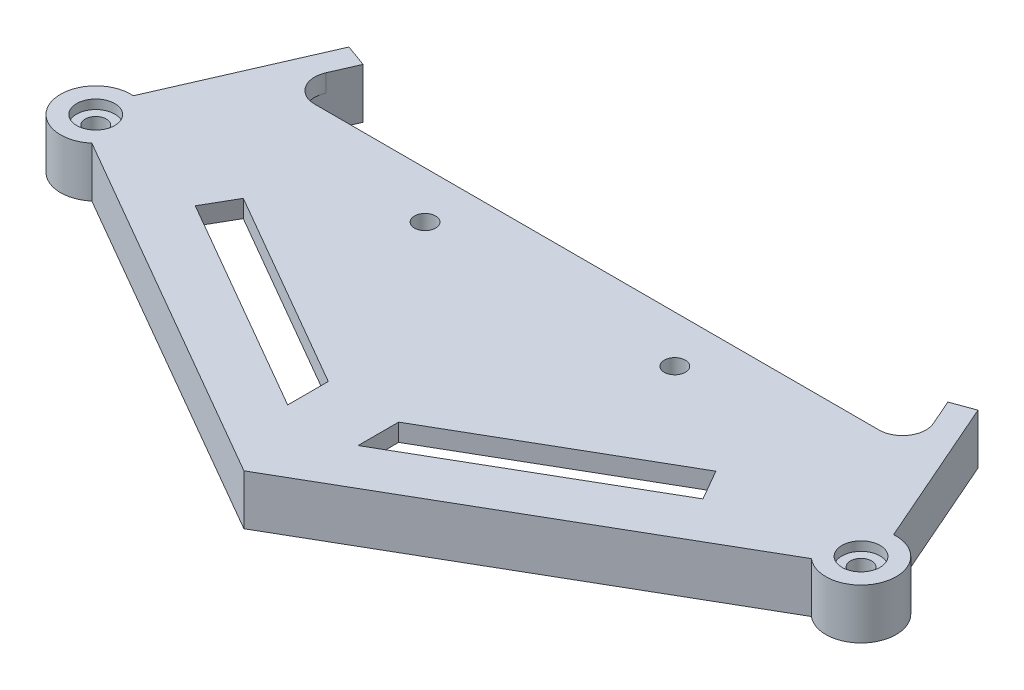
SolidWorks part; units mm, degrees
ref_plane "Front Plane" through (0, 0, 0) normal (0, 0, 1) x (1, 0, 0)
ref_plane "Top Plane" through (0, 0, 0) normal (0, 1, 0) x (1, 0, 0)
ref_plane "Right Plane" through (0, 0, 0) normal (1, 0, 0) x (0, 0, -1)
sketch "Sketch1" plane through (0, 0, 0) normal (0, 1, 0) x (1, 0, 0)
  line L0 (-2, 1.1547) -> (-61.3696, 35.4318)
  line L1 (-65.2686, 39.9923) -> (-42.6286, 26.921) construction
  line L2 (-2, 1.1547) -> (0, 0)
  line L3 (0, 4.6188) -> (-59.3696, 38.8959)
  line L4 (2, 1.1547) -> (0, 0)
  line L5 (2, 1.1547) -> (61.3696, 35.4318)
  line L6 (0, 4.6188) -> (59.3696, 38.8959)
  line L7 (-65.2686, 45.9923) -> (65.2686, 45.9923) construction
  line L8 (-65.2686, 39.9923) -> (-58.4065, 67.9795) construction
  line L9 (-58.4065, 67.9795) -> (-56.6964, 72.6779) construction
  line L10 (-56.6964, 72.6779) -> (-46.8296, 69.0867) construction
  line L11 (-46.8296, 69.0867) -> (-65.2686, 39.9923) construction
  line L12 (-51.763, 70.8823) -> (-65.2686, 39.9923) construction
  line L13 (-51.763, 70.8823) -> (-49.8799, 70.1969)
  line L14 (-49.8799, 70.1969) -> (-61.17, 44.3742)
  line L15 (-51.763, 70.8823) -> (-53.6461, 71.5677)
  line L16 (-53.6461, 71.5677) -> (-64.835, 45.9766)
  line L17 (0, 4.6188) -> (0, 66.7338) construction
  line L18 (49.8799, 70.1969) -> (61.17, 44.3742)
  line L19 (51.763, 70.8823) -> (49.8799, 70.1969)
  line L20 (51.763, 70.8823) -> (53.6461, 71.5677)
  line L21 (53.6461, 71.5677) -> (64.835, 45.9766)
  line L22 (-54.252, 60.1969) -> (54.252, 60.1969)
  line L23 (-49.8799, 70.1969) -> (49.8799, 70.1969) construction
  circle A0 centre (-65.2686, 39.9923) radius 6
  circle A1 centre (65.2686, 39.9923) radius 6
  circle A2 centre (-65.2686, 39.9923) radius 1.8
  circle A3 centre (65.2686, 39.9923) radius 1.8
  dimension "D1" = 12
  dimension "D7" = 3.6
  dimension "D8" = 3.6
  dimension "D2" = 2
  dimension "D3" = 68.5541
  dimension "D4" = 2.3094
  dimension "D5" = 68.5541
  dimension "D6" = 120
  dimension "D9" = 5
  dimension "D10" = 27.9872
  dimension "D11" = 34.4454
  dimension "D12" = 10.5
  dimension "D13" = 87.635
  dimension "D14" = 2
  dimension "D15" = 2
  dimension "D16" = 10
extrude "Boss-Extrude1" add sketch "Sketch1" along normal blind 4 contours A2 A0 | A1 L6 L3 A0 L0 L2 L4 L5 | A1 A3 | A1 L7 A0 L3 L6 | A0 L14 L13 L15 L16 | A1 L21 L20 L19 L18 region at (-31.041, 0, -19.4083) region at (-70.8075, 0, -38.172) region at (-57.3339, 0, -58.133) region at (0, 0, -39.497) region at (60.2194, 0, -37.0771) region at (57.3339, 0, -58.133)
fillet "Fillet1" radius 4 2 edges at (54.252, 2, -60.1969) (-54.252, 2, -60.1969)
sketch "Sketch2" plane through (0, 4, 0) normal (0, 1, 0) x (1, 0, 0)
  line L0 (-65.2686, 45.9923) -> (65.2686, 45.9923)
  line L4 (61.3696, 35.4318) -> (0, 0) construction
  line L5 (-61.3696, 35.4318) -> (0, 0)
  line L6 (0, 0) -> (61.3696, 35.4318)
  arc A0 (-64.835, 45.9766) -> (-61.3696, 35.4318) centre (-65.2686, 39.9923) ccw construction
  arc A1 (61.3696, 35.4318) -> (64.835, 45.9766) centre (65.2686, 39.9923) ccw construction
  arc A4 (65.2686, 45.9923) -> (61.3696, 35.4318) centre (65.2686, 39.9923) cw
  arc A5 (-65.2686, 45.9923) -> (-61.3696, 35.4318) centre (-65.2686, 39.9923) ccw
  circle A6 centre (-65.2686, 39.9923) radius 1.8
  circle A7 centre (65.2686, 39.9923) radius 1.8
extrude "Boss-Extrude2" [suppressed] add sketch "Sketch2" along normal blind 3 separate body
sketch "Sketch3" plane through (0, 0, 0) normal (0, -1, 0) x (1, 0, 0)
  circle A0 centre (-65.2686, -39.9923) radius 6
  circle A1 centre (65.2686, -39.9923) radius 6
extrude "Cut-Extrude1" [suppressed] cut sketch "Sketch3" against normal up to next
sketch "Sketch4" plane through (0, 4, 0) normal (0, 1, 0) x (1, 0, 0)
  line L5 (43.3013, 35) -> (40.3013, 40.1962)
  line L6 (40.3013, 40.1962) -> (0, 16.9282)
  line L7 (0, 10) -> (43.3013, 35)
  line L8 (-2, 1.1547) -> (-61.3696, 35.4318) construction
  line L15 (61.3696, 35.4318) -> (57.9342, 41.3821) construction
  line L16 (0, 0) -> (0, 10) construction
  line L17 (-43.3013, 35) -> (-40.3013, 40.1962)
  line L18 (0, 10) -> (-43.3013, 35)
  line L19 (-40.3013, 40.1962) -> (0, 16.9282)
  line L22 (0, 16.9282) -> (0, 45.9923) construction
  line L23 (-6, 20.3923) -> (-6, 13.4641)
  line L24 (6, 20.3923) -> (6, 13.4641)
  line L25 (2, 1.1547) -> (61.3696, 35.4318) construction
  dimension "D1" = 50
  dimension "D2" = 50
  dimension "D3" = 6
  dimension "D4" = 6
  dimension "D5" = 10
extrude "Cut-Extrude2" cut sketch "Sketch4" against normal up to next contours L7 L5 | L23 L19 L17 L18 region at (23.9111, 4, -27.2208) region at (-23.9111, 4, -27.2208)
sketch "Sketch5" plane through (0, 0, 0) normal (0, -1, 0) x (1, 0, 0)
  line L0 (-59.3696, -38.8959) -> (0, -4.6188)
  line L1 (0, -4.6188) -> (59.3696, -38.8959)
  line L2 (-61.3696, -35.4318) -> (0, 0)
  line L3 (0, 0) -> (61.3696, -35.4318)
  line L4 (61.17, -44.3742) -> (49.8799, -70.1969)
  line L5 (49.8799, -70.1969) -> (53.6461, -71.5677)
  line L6 (53.6461, -71.5677) -> (64.835, -45.9766)
  line L7 (-65.2686, -45.9923) -> (-53.6461, -71.5677)
  line L8 (-53.6461, -71.5677) -> (-49.8799, -70.1969)
  line L9 (-49.8799, -70.1969) -> (-61.17, -44.3742)
  arc A0 (59.3696, -38.8959) -> (61.3696, -35.4318) centre (65.2686, -39.9923) cw
  arc A1 (-61.3696, -35.4318) -> (-59.3696, -38.8959) centre (-65.2686, -39.9923) cw
  circle A2 centre (-65.2686, -39.9923) radius 6 construction
  arc A3 (61.17, -44.3742) -> (65.2686, -45.9923) centre (65.2686, -39.9923) ccw
  arc A4 (-61.17, -44.3742) -> (-65.2686, -45.9923) centre (-65.2686, -39.9923) cw
  line M7 (61.3696, -35.4318) -> (0, 0)
  line M8 (0, 0) -> (-61.3696, -35.4318)
  line M26 (-64.835, -45.9766) -> (-53.6461, -71.5677)
  line M27 (-53.6461, -71.5677) -> (-49.8799, -70.1969)
  line M28 (-49.8799, -70.1969) -> (-51.8026, -65.7993)
  line M32 (51.8026, -65.7993) -> (49.8799, -70.1969)
  line M33 (49.8799, -70.1969) -> (53.6461, -71.5677)
  line M34 (53.6461, -71.5677) -> (64.835, -45.9766)
extrude "Boss-Extrude3" add sketch "Sketch5" along normal blind 5.558 contours L9 A4 M26 M27 M28 | A1 L0 L1 A0 M8 M7 | A3 L4 M32 M33 M34 region at (-58.9574, 0, -36.3485) region at (57.3339, 0, -58.133) region at (-57.3339, 0, -58.133)
sketch "Sketch6" plane through (0, 0, 0) normal (0, -1, 0) x (1, 0, 0)
  line L0 (-21.3, -52.1969) -> (21.3, -52.1969) construction
  line L1 (-65.2686, -45.9923) -> (65.2686, -45.9923) construction
  line L2 (-54.252, -60.1969) -> (54.252, -60.1969) construction
  circle A0 centre (-21.3, -52.1969) radius 1.8
  circle A1 centre (21.3, -52.1969) radius 1.8
  point P4 (0, -52.1969)
  point P7 (0, -45.9923)
  dimension "D3" = 3.6
  dimension "D1" = 42.6
  dimension "D2" = 8
extrude "Cut-Extrude3" cut sketch "Sketch6" against normal through all contours A1 | A0 region at (21.3, 0, -52.1969)
ref_plane "Plane1" through (0, 0, 0) normal (0, 0, -1) x (-1, 0, 0)
sketch "Sketch16" plane through (0, 4, 0) normal (0, 1, 0) x (1, 0, 0)
  line L0 (-21.3, 52.1969) -> (-14.3, 35.6969) construction
  line L1 (-14.3, 35.6969) -> (14.3, 35.6969) construction
  line L2 (14.3, 35.6969) -> (21.3, 52.1969) construction
  line L3 (21.3, 52.1969) -> (-21.3, 52.1969) construction
  line L4 (14.4324, 35.4969) -> (28.523, 55.9969)
  line L5 (-14.4324, 35.4969) -> (14.4324, 35.4969)
  line L6 (28.523, 55.9969) -> (-28.523, 55.9969)
  line L7 (-21.4841, 52.1188) -> (-14.4324, 35.4969) construction
  line L8 (14.4324, 35.4969) -> (21.4841, 52.1188) construction
  line L9 (-28.523, 55.9969) -> (-14.4324, 35.4969)
  line L10 (-54.252, 60.1969) -> (54.252, 60.1969) construction
  line L11 (24.4316, 50.0444) -> (22.7834, 51.1773) construction
  line L12 (22.7834, 51.1773) -> (23.7836, 52.6325) construction
  circle A0 centre (-21.3, 52.1969) radius 1.8 construction
  circle A1 centre (21.3, 52.1969) radius 1.8 construction
  point P12 (-21.3, 53.9969)
  point P13 (21.3, 53.9969)
  dimension "D1" = 17.9234
  dimension "D2" = 28.6
  dimension "D3" = 17.9234
  dimension "D4" = 42.6
  dimension "D6" = 2
  dimension "D7" = 2
  dimension "D5" = 0.2
sketch "Sketch17" plane through (0, 0, 0) normal (0, -1, 0) x (1, 0, 0)
  circle A0 centre (65.2686, -39.9923) radius 1.8
  circle A1 centre (65.2686, -39.9923) radius 6
  circle A2 centre (-65.2686, -39.9923) radius 1.8
  circle A3 centre (-65.2686, -39.9923) radius 6
extrude "Boss-Extrude6" add sketch "Sketch17" along normal blind 0.56
sketch "Sketch18" plane through (0, 4, 0) normal (0, 1, 0) x (1, 0, 0)
  circle A0 centre (-65.2686, 39.9923) radius 1.8
  circle A1 centre (-65.2686, 39.9923) radius 6
  circle A2 centre (65.2686, 39.9923) radius 1.8
  circle A3 centre (65.2686, 39.9923) radius 6
extrude "Cut-Extrude13" cut sketch "Sketch18" against normal blind 2.56
sketch "Sketch19" plane through (0, -0.56, 0) normal (0, -1, 0) x (1, 0, 0)
  circle A0 centre (-65.2686, -39.9923) radius 3.25
  circle A1 centre (-65.2686, -39.9923) radius 6
  circle A2 centre (65.2686, -39.9923) radius 3.25
  circle A3 centre (65.2686, -39.9923) radius 6
  dimension "D1" = 6.5
  dimension "D2" = 6.5
extrude "Boss-Extrude7" add sketch "Sketch19" along normal up to surface (4.998 mm away) up to face at (0, -5.558, -25.4885)
sketch "Sketch20" plane through (0, 1.44, 0) normal (0, 1, 0) x (1, 0, 0)
  circle A0 centre (-65.2686, 39.9923) radius 3.25
  circle A1 centre (-65.2686, 39.9923) radius 6
  circle A2 centre (65.2686, 39.9923) radius 3.25
  circle A3 centre (65.2686, 39.9923) radius 6
  dimension "D1" = 6.5
  dimension "D2" = 6.5
extrude "Boss-Extrude8" add sketch "Sketch20" along normal up to surface (2.56 mm away) up to face at (0, 4, -53.7445)
sketch "Sketch7" plane through (0, 0, 0) normal (0, 0, -1) x (-1, 0, 0)
  line L4 (-12, -22.0098) -> (12, -22.0098)
  line L5 (-12, -22.0098) -> (-12, 2.0098)
  line L6 (-12, 2.0098) -> (12, 2.0098)
  line L7 (12, -22.0098) -> (12, 2.0098)
  line L8 (-12, -22.0098) -> (12, 2.0098) construction
  line L9 (-12, 2.0098) -> (12, -22.0098) construction
  circle A1 centre (0, -10) radius 12 construction
  dimension "D1" = 24
  dimension "D2" = 14
extrude "Boss-Extrude4" [suppressed] add sketch "Sketch7" along normal blind 7 contours L5 A1 | L5 A1
sketch "Sketch8" [suppressed] plane through (0, 0, 0) normal (0, 0, 1) x (1, 0, 0)
  line L0 (12, 2.0098) -> (0, 2.0098) construction
  line L1 (9.8727, -10) -> (4.9363, -1.45)
  line L2 (4.9363, -1.45) -> (-4.9363, -1.45)
  line L3 (-4.9363, -1.45) -> (-9.8727, -10)
  line L4 (-9.8727, -10) -> (-4.9363, -18.55)
  line L5 (-4.9363, -18.55) -> (4.9363, -18.55)
  line L6 (4.9363, -18.55) -> (9.8727, -10)
  circle A0 centre (0, -10) radius 8.55 construction
  dimension "D1" = 14
  dimension "D2" = 17.1
extrude "Cut-Extrude5" [suppressed] cut sketch "Sketch8" against normal blind 4
sketch "Sketch9" [suppressed] plane through (0, 0, -4) normal (0, 0, 1) x (1, 0, 0)
  circle A0 centre (0, -10) radius 7.5
  dimension "D1" = 15
extrude "Cut-Extrude6" [suppressed] cut sketch "Sketch9" against normal blind 1000
sketch "Sketch10" plane through (0, 4, 0) normal (0, 1, 0) x (1, 0, 0)
  line L0 (-81.8328, 55.5934) -> (83.8701, 55.5934)
  line L1 (83.8701, 55.5934) -> (83.8701, -6.6584)
  line L2 (83.8701, -6.6584) -> (-81.8328, -5.8661)
  line L3 (-81.8328, -5.8661) -> (-81.8328, 55.5934)
extrude "Cut-Extrude7" [suppressed] cut sketch "Sketch10" against normal up to surface (1.9902 mm away)
sketch "Sketch11" [suppressed] plane through (0, 2.0098, 0) normal (0, 1, 0) x (1, 0, 0)
  line L0 (-2, 1.1547) -> (-61.3696, 35.4318) construction
  line L1 (-61.3696, 35.4318) -> (-12, 6.9282)
  line L2 (-12, 6.9282) -> (-12, 0)
  line L3 (2.2, 0) -> (-2.2, 0) construction
  line L4 (-12, 0) -> (12, 0)
  line L5 (12, 0) -> (12, 6.9282)
  line L6 (12, 6.9282) -> (12, 0) construction
  line L7 (12, 6.9282) -> (61.3696, 35.4318)
  line L8 (-65.2686, 45.9923) -> (65.2686, 45.9923)
  line L9 (2, 1.1547) -> (61.3696, 35.4318) construction
  line L10 (-43.6113, 40.1901) -> (-45.6113, 36.726)
  line L11 (-45.6113, 36.726) -> (0, 10.3923)
  line L12 (0, 10.3923) -> (45.6113, 36.726)
  line L13 (45.6113, 36.726) -> (43.6113, 40.1901)
  line L14 (43.6113, 40.1901) -> (0, 15.0111)
  line L15 (0, 15.0111) -> (-43.6113, 40.1901)
  line L16 (-45.6113, 36.726) -> (-4, 12.7017) construction
  arc A0 (-65.2686, 45.9923) -> (-61.3696, 35.4318) centre (-65.2686, 39.9923) ccw
  circle A1 centre (65.2686, 39.9923) radius 6 construction
  arc A2 (65.2686, 45.9923) -> (61.3696, 35.4318) centre (65.2686, 39.9923) cw
  arc A3 (61.3696, 35.4318) -> (64.835, 45.9766) centre (65.2686, 39.9923) ccw construction
  circle A4 centre (-65.2686, 39.9923) radius 1.8
  circle A5 centre (-21.3, 52.1969) radius 1.8
  circle A6 centre (21.3, 52.1969) radius 1.8
  circle A7 centre (65.2686, 39.9923) radius 1.8
  circle A8 centre (-65.2686, 39.9923) radius 1.8 construction
  circle A9 centre (-21.3, 52.1969) radius 1.8 construction
  circle A10 centre (21.3, 52.1969) radius 1.8 construction
  circle A13 centre (65.2686, 39.9923) radius 1.8 construction
sketch "Sketch12" [suppressed] plane through (0, 0, 0) normal (0, 0, 1) x (1, 0, 0)
  line L0 (0, 2.0098) -> (0, -21.9902)
  line L1 (-12, -21.9902) -> (12, -21.9902)
  line L2 (12, -22.0098) -> (12, 2.0098) construction
  line L3 (12, -21.9902) -> (12, -22.0098)
  line L4 (12, -22.0098) -> (-12, -22.0098)
  line L5 (-12, -22.0098) -> (-12, -21.9902)
  line L6 (0, 2.0098) -> (-43.6113, 2.0098) construction
  point P9 (0, -21.9902)
  line M8 (-12, -22.0098) -> (12, -22.0098)
  line M9 (12, -22.0098) -> (12, 2.0098)
  line M11 (-12, 2.0098) -> (-12, -22.0098)
  dimension "D1" = 24
extrude "Cut-Extrude8" [suppressed] cut sketch "Sketch12" against normal through all both and the other way through all contours L1 M11 M8 M9 | L1 L3 L4 L5
sketch "Sketch13" [suppressed] plane through (0, 0, 0) normal (0, 0, 1) x (1, 0, 0)
  line L0 (-12, -9.9902) -> (-12.1878, -9.9902)
  line L1 (-12, -21.9902) -> (-12, 2.0098) construction
  line L2 (-12.1878, -9.9902) -> (-6.091, -20.55)
  line L3 (-6.091, -20.55) -> (6.091, -20.55)
  line L4 (6.091, -20.55) -> (12.1878, -9.9902)
  line L5 (12.1878, -9.9902) -> (12, -9.9902)
  line L6 (12, -21.9902) -> (12, 2.0098) construction
  line L7 (-9.8727, -10) -> (-4.9363, -18.55) construction
  line L8 (4.9363, -18.55) -> (9.8727, -10) construction
  line L9 (-4.9363, -18.55) -> (4.9363, -18.55) construction
  line L10 (-9.8727, -10) -> (-4.9363, -18.55) construction
  line L11 (4.9363, -18.55) -> (9.8727, -10) construction
  line L12 (-12, -9.9902) -> (-12, -21.9902)
  line L13 (-12, -21.9902) -> (12, -21.9902)
  line L14 (12, -21.9902) -> (12, -9.9902)
  line M10 (-12, -21.9902) -> (12, -21.9902)
  line M11 (12, -21.9902) -> (12, 2.0098)
  line M13 (-12, 2.0098) -> (-12, -21.9902)
  dimension "D1" = 2
  dimension "D2" = 2
  dimension "D3" = 2
extrude "Cut-Extrude10" [suppressed] cut sketch "Sketch13" against normal up to surface and the other way through all contours L4 L3 L2 M13 M10 M11
sketch "Sketch14" plane through (0, 0, 0) normal (0, -1, 0) x (1, 0, 0)
  circle A0 centre (-65.2686, -39.9923) radius 6
  circle A1 centre (-65.2686, -39.9923) radius 1.8
  circle A2 centre (65.2686, -39.9923) radius 1.8
  circle A3 centre (65.2686, -39.9923) radius 6
extrude "Boss-Extrude5" [suppressed] add sketch "Sketch14" along normal blind 2.56
sketch "Sketch15" [suppressed] plane through (0, 2.0098, 0) normal (0, 1, 0) x (1, 0, 0)
  circle A0 centre (-65.2686, 39.9923) radius 3.25
  circle A1 centre (65.2686, 39.9923) radius 3.25
  dimension "D1" = 6.5
extrude "Cut-Extrude11" [suppressed] cut sketch "Sketch15" against normal blind 2.57
sketch "Sketch21" plane through (0, 4, 0) normal (0, 1, 0) x (1, 0, 0)
  line L1 (-92.2075, 80.0884) -> (87.9344, 80.0884)
  line L2 (-92.2075, 80.0884) -> (-92.2075, -7.5087)
  line L3 (-92.2075, -7.5087) -> (87.9344, -7.5087)
  line L4 (87.9344, 80.0884) -> (87.9344, -7.5087)
extrude "Cut-Extrude14" cut sketch "Sketch21" against normal blind 1
